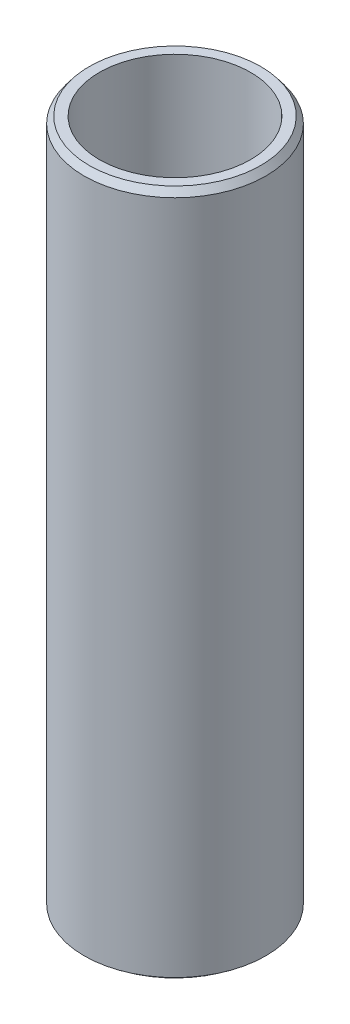
SolidWorks part; units mm, degrees
ref_plane "Front Plane" through (0, 0, 0) normal (0, 0, 1) x (1, 0, 0)
ref_plane "Top Plane" through (0, 0, 0) normal (0, 1, 0) x (1, 0, 0)
ref_plane "Right Plane" through (0, 0, 0) normal (1, 0, 0) x (0, 0, -1)
sketch "Sketch1" plane through (0, 0, 0) normal (0, 1, 0) x (1, 0, 0)
  circle A0 centre (0, 0) radius 35
  dimension "SHAFT_OD" = 70
extrude "Boss-Extrude1" add sketch "Sketch1" along normal blind 264.8236
sketch "Sketch2" plane through (0, 0, 0) normal (0, 1, 0) x (1, 0, 0)
  circle A0 centre (0, 0) radius 29.1589
  dimension "BORE_D" = 58.3179
extrude "Cut-Extrude1" cut sketch "Sketch2" along normal through all
chamfer "Chamfer1" distance 2.5539 angle 37.252 2 edges at (0, 264.8236, 35) (0, 0, 35) first distance on face at (0, 264.8236, 35) first distance on face at (0, 0, 29.1589)
